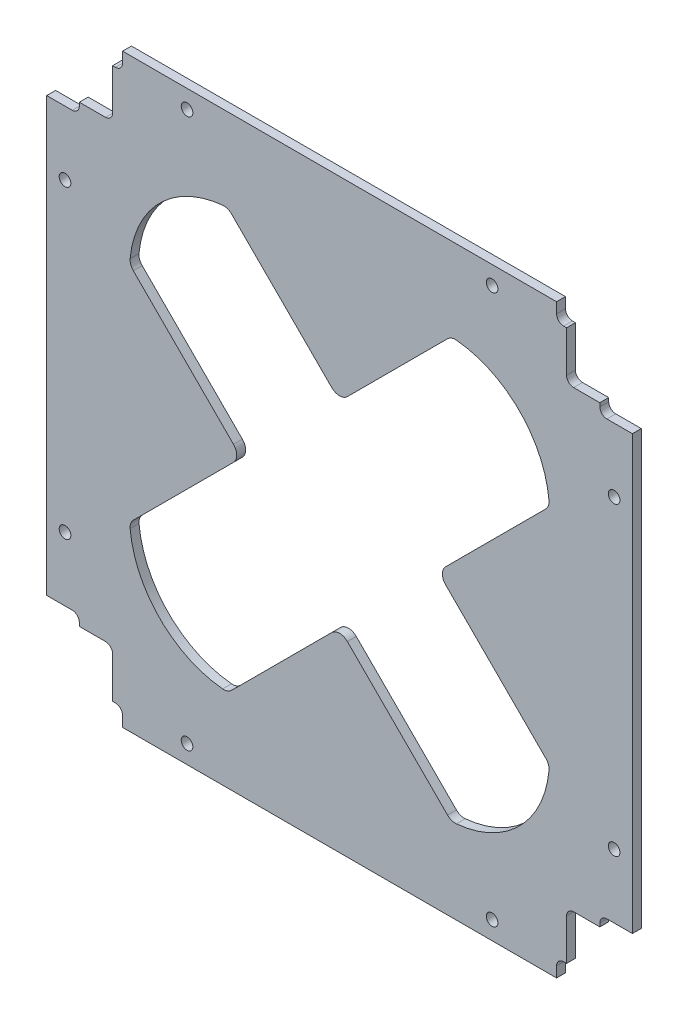
SolidWorks part; units mm, degrees
material "FR4_stuffedProtoboard"
ref_plane "Front Plane" through (0, 0, 0) normal (0, 0, 1) x (1, 0, 0)
ref_plane "Top Plane" through (0, 0, 0) normal (0, 1, 0) x (1, 0, 0)
ref_plane "Right Plane" through (0, 0, 0) normal (1, 0, 0) x (0, 0, -1)
sketch "Sketch1" plane through (0, 0, 0) normal (0, 0, 1) x (1, 0, 0)
  line L0 (53, 53) -> (-53, -53) construction
  line L1 (53, 53) -> (-53, 53)
  line L2 (53, 53) -> (53, -53)
  line L3 (53, -53) -> (-53, -53)
  line L4 (-53, 53) -> (-53, -53)
  point P4 (0, 0)
  dimension "D1" = 106
  dimension "D2" = 106
extrude "mainOutline" add sketch "Sketch1" along normal blind 1.6
sketch "axisLabels" plane through (0, 0, 0) normal (0, 0, -1) x (-1, 0, 0)
  text T0 "+Y"
  text T1 "+X"
sketch "Sketch4" plane through (0, 0, 0) normal (0, 0, -1) x (-1, 0, 0)
  line L10 (-53, 53) -> (53, 53) construction
  line L29 (41.3, 53) -> (41.3, 41.3)
  line L31 (53, 41.3) -> (41.3, 41.3)
  line L46 (53, 53) -> (53, -53) construction
  line L51 (53, 41.3) -> (53, 53)
  line L52 (53, 53) -> (41.3, 53)
  dimension "D11" = 11.7
  dimension "D12" = 11.7
extrude "railCutouts" cut sketch "Sketch4" against normal through all
sketch "Sketch13" plane through (0, 0, 0) normal (0, 0, -1) x (-1, 0, 0)
  line L0 (47.3, 39.4) -> (47.3, 41.3)
  line L2 (53, 41.3) -> (53, 39.4)
  line L5 (41.3, 53) -> (39.5, 53)
  line L6 (41.3, 53) -> (41.3, 50)
  line L7 (41.3, 50) -> (39.5, 50)
  line L8 (39.5, 53) -> (39.5, 50)
  line L9 (53, 41.3) -> (53, -53) construction
  line L10 (53, 41.3) -> (47.3, 41.3)
  line L12 (53, 39.4) -> (47.3, 39.4)
  line L13 (41.3, 41.3) -> (53, 41.3) construction
  point P1 (0, 0)
  point P3 (47.3, 41.3)
  point P17 (47.15, 41.3)
  dimension "D1" = 5.7
  dimension "D3" = 1.9
  dimension "D5" = 1.8
  dimension "D6" = 3
extrude "filletCutouts" cut sketch "Sketch13" against normal through all both and the other way through all
sketch "Sketch5" plane through (0, 0, 0) normal (0, 0, -1) x (-1, 0, 0)
  line L23 (42.198, 42.198) -> (45.4803, 45.4803) construction
  line L24 (41.3, 43.0961) -> (44.5823, 46.3784)
  line L25 (43.0961, 41.3) -> (46.3784, 44.5823)
  line L41 (41.3, 50) -> (41.3, 41.3) construction
  arc A14 (41.3, 43.0961) -> (43.0961, 41.3) centre (42.198, 42.198) ccw
  arc A15 (46.3784, 44.5823) -> (44.5823, 46.3784) centre (45.4803, 45.4803) ccw
  point P0 (41.3, 41.3)
  point P52 (43.8392, 43.8392)
  dimension "D14" = 1.27
  dimension "D7" = 45
extrude "dogbone" [suppressed] cut sketch "Sketch5" against normal through all
sketch "Sketch14" plane through (0, 0, 1.6) normal (0, 0, 1) x (1, 0, 0)
  point P1 (-47.3, 39.4)
sketch "Sketch27" plane through (0, 0, 1.6) normal (0, 0, 1) x (1, 0, 0)
  line L0 (-40.928, 42.198) -> (-40.928, 49.628)
  line L1 (-48.198, 39.028) -> (-53, 39.028)
  line L2 (-53, 39.4) -> (-53, -53) construction
  line L3 (-53, 39.028) -> (-53, 53)
  line L4 (-53, 53) -> (-39.128, 53)
  line L5 (-39.128, 53) -> (-39.128, 50.898)
  line L6 (-40.928, 49.628) -> (-40.398, 49.628)
  line L7 (-42.198, 40.928) -> (-46.928, 40.928)
  line L8 (-46.928, 40.928) -> (-46.928, 40.298)
  line L10 (53, 53) -> (-39.5, 53) construction
  arc A0 (-42.198, 40.928) -> (-40.928, 42.198) centre (-42.198, 42.198) ccw
  arc A1 (-40.398, 49.628) -> (-39.128, 50.898) centre (-40.398, 50.898) ccw
  arc A2 (-48.198, 39.028) -> (-46.928, 40.298) centre (-48.198, 40.298) ccw
  point P7 (0, 0)
  dimension "D1" = 1.27
extrude "smoothCorner" cut sketch "Sketch27" against normal blind 10
pattern_sketch "Sketch-Pattern1" [suppressed] of bodies 103 driven by "Sketch14"
mirror "Mirror1" about plane through (0, 0, 0) normal (1, 0, 0) of "smoothCorner", "filletCutouts", "railCutouts"
mirror "Mirror2" about plane through (0, 0, 0) normal (0, 1, 0) of "Mirror1"
fillet "Fillet1" [suppressed] radius 0.5
sketch "Sketch6" [suppressed] plane through (0, 0, 0) normal (0, 0, -1) x (-1, 0, 0)
  line L0 (-39, 50) -> (-39, 53) construction
  line L1 (-39, 49) -> (-39, 53) construction
  line L2 (-53, 53) -> (41.3, 53) construction
  line L3 (-40, 50) -> (-40, 53)
  line L4 (-38, 50) -> (-38, 53)
  line L5 (-49, 39) -> (-53, 39) construction
  line L6 (-53, 39) -> (-48, 39) construction
  line L7 (-49, 38) -> (-53, 38)
  line L8 (-49, 40) -> (-53, 40)
  line L9 (-49, -39) -> (-55.2142, -39) construction
  line L10 (-48, -39) -> (-53, -39) construction
  line L11 (-49, -40) -> (-55.2142, -40)
  line L12 (-49, -38) -> (-55.2142, -38)
  line L13 (-39, -50) -> (-39, -53.9161) construction
  line L14 (-39, -53) -> (-39, -49) construction
  line L15 (-38, -50) -> (-38, -53.9161)
  line L16 (-40, -50) -> (-40, -53.9161)
  line L17 (39, -50.9) -> (39, -54.538) construction
  line L18 (39, -49.9) -> (39, -53) construction
  line L19 (40, -50.9) -> (40, -54.538)
  line L20 (38, -50.9) -> (38, -54.538)
  line L21 (49, -40.5) -> (54.2026, -40.5) construction
  line L22 (53, -40.5) -> (48, -40.5) construction
  line L23 (49, -39.5) -> (54.2026, -39.5)
  line L24 (49, -41.5) -> (54.2026, -41.5)
  line L25 (49, 40.5) -> (54.5566, 40.5) construction
  line L26 (48, 40.5) -> (53, 40.5) construction
  line L27 (49, 41.5) -> (54.5566, 41.5)
  line L28 (49, 39.5) -> (54.5566, 39.5)
  line L29 (39, 50.9) -> (39, 55.8281) construction
  line L30 (39, 53) -> (39, 49.9) construction
  line L31 (38, 50.9) -> (38, 55.8281)
  line L32 (40, 50.9) -> (40, 55.8281)
  line L33 (-48, -41.4) -> (-48, -39) construction
  line L34 (-39, -49) -> (-41.4, -49) construction
  line L35 (41.4, -49.9) -> (39, -49.9) construction
  line L36 (48, -40.5) -> (48, -41.4) construction
  line L37 (48, 41.4) -> (48, 40.5) construction
  line L38 (39, 49.9) -> (41.4, 49.9) construction
  arc A0 (-40, 50) -> (-38, 50) centre (-39, 50) ccw
  arc A1 (-38, 53) -> (-40, 53) centre (-39, 53) ccw
  arc A2 (-49, 38) -> (-49, 40) centre (-49, 39) ccw
  arc A3 (-53, 40) -> (-53, 38) centre (-53, 39) ccw
  arc A4 (-49, -40) -> (-49, -38) centre (-49, -39) ccw
  arc A5 (-55.2142, -38) -> (-55.2142, -40) centre (-55.2142, -39) ccw
  arc A6 (-38, -50) -> (-40, -50) centre (-39, -50) ccw
  arc A7 (-40, -53.9161) -> (-38, -53.9161) centre (-39, -53.9161) ccw
  arc A8 (40, -50.9) -> (38, -50.9) centre (39, -50.9) ccw
  arc A9 (38, -54.538) -> (40, -54.538) centre (39, -54.538) ccw
  arc A10 (49, -39.5) -> (49, -41.5) centre (49, -40.5) ccw
  arc A11 (54.2026, -41.5) -> (54.2026, -39.5) centre (54.2026, -40.5) ccw
  arc A12 (49, 41.5) -> (49, 39.5) centre (49, 40.5) ccw
  arc A13 (54.5566, 39.5) -> (54.5566, 41.5) centre (54.5566, 40.5) ccw
  arc A14 (38, 50.9) -> (40, 50.9) centre (39, 50.9) ccw
  arc A15 (40, 55.8281) -> (38, 55.8281) centre (39, 55.8281) ccw
  point P6 (-39, 51.5)
  point P11 (-51, 39)
  point P21 (-52.1071, -39)
  point P30 (-39, -51.958)
  point P39 (39, -52.719)
  point P48 (51.6013, -40.5)
  point P57 (51.7783, 40.5)
  point P66 (39, 53.364)
  point P75 (-39, 49)
  dimension "D1" = 1
extrude "solarFillets" [suppressed] cut sketch "Sketch6" against normal through all
fillet "handlingFillets" [suppressed] radius 1
sketch "Sketch7" plane through (0, 0, 1.6) normal (0, 0, 1) x (1, 0, 0)
  line L0 (-39.128, -53) -> (39.128, -53) construction
  line L1 (-53, 39.028) -> (-53, -39.028) construction
  line L2 (39.128, 53) -> (-39.128, 53) construction
  line L3 (-31.37, 28.67) -> (-31.37, 31.21) construction
  line L4 (-31.37, 31.21) -> (-28.83, 31.21) construction
  line L5 (-28.83, 31.21) -> (-28.83, 28.67) construction
  line L6 (-28.83, 28.67) -> (-31.37, 28.67) construction
  line L7 (-31.37, 28.67) -> (-28.83, 31.21) construction
  circle A1 centre (-28.4723, -17.925) radius 0.8
  circle A3 centre (-28.4723, -33.775) radius 0.8
  circle A5 centre (-31.37, 28.67) radius 0.425
  circle A7 centre (-28.83, 28.67) radius 0.425
  circle A9 centre (-30.1, 29.94) radius 0.425
  circle A10 centre (-28.83, 31.21) radius 0.425
  circle A11 centre (-31.37, 31.21) radius 0.425
  circle A12 centre (-31.37, 21.27) radius 0.425
  circle A13 centre (-28.83, 21.27) radius 0.425
  circle A14 centre (-30.1, 22.54) radius 0.425
  circle A15 centre (-28.83, 23.81) radius 0.425
  circle A16 centre (-31.37, 23.81) radius 0.425
  circle A17 centre (-31.37, 13.87) radius 0.425
  circle A18 centre (-28.83, 13.87) radius 0.425
  circle A19 centre (-30.1, 15.14) radius 0.425
  circle A20 centre (-28.83, 16.41) radius 0.425
  circle A21 centre (-31.37, 16.41) radius 0.425
  point P13 (-30.1, 29.94)
  dimension "D8" = 1.6
  dimension "D9" = 3
  dimension "D6" = 0.85
  dimension "D1" = 19.225
  dimension "D2" = 24.5277
  dimension "D3" = 15.85
  dimension "D4" = 23.06
  dimension "D5" = 22.9
  dimension "D7" = 2.54
  dimension "D10" = 7.4
extrude "connectorHoles" [suppressed] cut sketch "Sketch7" against normal through all
hole_wizard "M2 Clearance Hole1" positions "Sketch8" profile "Sketch9" hole size "M2" standard "ANSI Metric" end condition through all
sketch "Sketch8" plane through (0, 0, 0) normal (0, 0, -1) x (-1, 0, 0)
  line L0 (53, 39.028) -> (53, -39.028) construction
  line L1 (39.128, -53) -> (-39.128, -53) construction
  line L2 (-53, -39.028) -> (-53, 39.028) construction
  line L3 (53, 0) -> (-53, 0) construction
  line L5 (0, -53) -> (0, -11.6379) construction
  line L6 (53, 39.028) -> (53, -39.028) construction
  point P0 (49.5, -27.5)
  point P1 (27.5, -49.5)
  point P5 (-49.5, -27.5)
  point P30 (-27.5, -49.5)
  point P31 (-27.5, 49.5)
  point P32 (-49.5, 27.5)
  point P33 (27.5, 49.5)
  point P34 (49.5, 27.5)
  dimension "D1" = 3.5
  dimension "D2" = 3.5
  dimension "D3" = 55
  dimension "D4" = 3.5
  dimension "D5" = 55
  dimension "D6" = 55
sketch "Sketch9" plane through (-49.5, -27.5, 0) normal (1, 0, 0) x (0, 1, 0)
  line L0 (0, 0) -> (0, 1.6)
  line L1 (0, 1.6) -> (1.05, 1.6)
  line L2 (1.05, 1.6) -> (1.05, 0)
  line L5 (1.05, 0) -> (0, 0)
  line L11 (0, -6.35) -> (0, 107.95) construction
  dimension "Thru Hole Dia." = 2.1
  dimension "Thru Hole Depth" = 1.6
sketch "Sketch12" plane through (0, 0, 1.6) normal (0, 0, 1) x (1, 0, 0)
  line L1 (-39.128, -53) -> (39.128, -53) construction
  line L2 (53, -39.028) -> (53, 39.028) construction
  circle A0 centre (27.815, -42.5) radius 0.8
  circle A1 centre (38.585, -42.5) radius 0.8
  dimension "D1" = 1.6
  dimension "D2" = 10.77
  dimension "D3" = 10.5
  dimension "D4" = 25.185
extrude "interboardConnectorHoles" [suppressed] cut sketch "Sketch12" against normal through all both and the other way through all
sketch "Sketch17" [suppressed] plane through (0, 0, 1.6) normal (0, 0, 1) x (1, 0, 0)
  line L1 (-35.8, -40) -> (-21.8, -40)
  line L2 (-35.8, -40) -> (-35.8, -45)
  line L3 (-35.8, -45) -> (-21.8, -45)
  line L4 (-21.8, -40) -> (-21.8, -45)
  line L5 (-41.3, -50) -> (-41.3, -43.2836) construction
  line L6 (-38.9, -53) -> (38.9, -53) construction
  dimension "D1" = 8
  dimension "D2" = 13
  dimension "D3" = 19.5
  dimension "D4" = 14
  dimension "D5" = 5.5
extrude "Cut-Extrude7" [suppressed] cut sketch "Sketch17" against normal through all both and the other way through all
fillet "Fillet2" [suppressed] radius 1.27
sketch "Sketch11" [suppressed] plane through (0, 0, 0) normal (0, 0, -1) x (-1, 0, 0)
  circle A0 centre (0, 0) radius 36
  dimension "D1" = 72
extrude "Cut-Extrude2" [suppressed] cut sketch "Sketch11" against normal through all both and the other way through all
sketch "Sketch15" plane through (0, 0, 0) normal (0, 0, -1) x (-1, 0, 0)
  line L0 (-39.128, 53) -> (39.128, 53) construction
  line L1 (45, 53) -> (-45, 53)
  line L2 (45, 53) -> (45, 46.8)
  line L3 (45, 46.8) -> (-45, 46.8)
  line L4 (-45, 53) -> (-45, 46.8)
  line L5 (45, -53) -> (-45, -53)
  line L6 (45, -53) -> (45, -46.8)
  line L7 (45, -46.8) -> (-45, -46.8)
  line L8 (-45, -53) -> (-45, -46.8)
  line L9 (39.128, -53) -> (-39.128, -53) construction
  line L10 (-53, -39.028) -> (-53, 39.028) construction
  line L11 (-53, 45) -> (-47.8, 45)
  line L12 (-53, 45) -> (-53, -45)
  line L13 (-53, -45) -> (-47.8, -45)
  line L14 (-47.8, 45) -> (-47.8, -45)
  line L15 (53, 45) -> (47.8, 45)
  line L16 (53, 45) -> (53, -45)
  line L17 (53, -45) -> (47.8, -45)
  line L18 (47.8, 45) -> (47.8, -45)
  line L19 (53, 39.028) -> (53, -39.028) construction
  point P8 (0, 53)
  point P11 (0, -53)
  point P22 (-53, 0)
  point P25 (53, 0)
  dimension "D1" = 90
  dimension "D3" = 6.2
  dimension "D5" = 5.2
extrude "Cut-Extrude5" cut sketch "Sketch15" against normal blind 0.001
sketch "Sketch18" [suppressed] plane through (0, 0, 1.6) normal (0, 0, 1) x (1, 0, 0)
  line L0 (-43.2836, -41.3) -> (-46.4, -41.3) construction
  line L1 (-44.8418, -41.3) -> (-41.3, -41.3)
  line L2 (-44.8418, -41.3) -> (-44.8418, -36.3)
  line L3 (-44.8418, -36.3) -> (-41.3, -36.3)
  line L4 (-41.3, -41.3) -> (-41.3, -36.3)
  line L5 (-41.3, -50) -> (-41.3, -43.2836) construction
  dimension "D1" = 5
extrude "Boss-Extrude1" [suppressed] add sketch "Sketch18" against normal up to surface (1.6 mm away) up to face at (0, 0, 0)
sketch "Sketch16" [suppressed] plane through (0, 0, 1.6) normal (0, 0, 1) x (1, 0, 0)
  line L4 (-45, -53) -> (45, -53)
  line L5 (45, -53) -> (45, -46.8)
  line L6 (45, -46.8) -> (-45, -46.8)
  line L7 (-45, -46.8) -> (-45, -53)
  line L8 (-45, -53) -> (45, -53)
  line L9 (45, -53) -> (45, -46.8)
  line L10 (45, -46.8) -> (-45, -46.8)
  line L11 (-45, -46.8) -> (-45, -53)
  line L12 (45, 53) -> (-45, 53)
  line L13 (45, 46.8) -> (45, 53)
  line L14 (-45, 46.8) -> (45, 46.8)
  line L15 (-45, 53) -> (-45, 46.8)
  line L16 (45, 53) -> (-45, 53)
  line L17 (45, 46.8) -> (45, 53)
  line L18 (-45, 46.8) -> (45, 46.8)
  line L19 (-45, 53) -> (-45, 46.8)
  line L20 (-47.8, 45) -> (-53, 45)
  line L21 (-53, 45) -> (-53, -45)
  line L22 (-53, -45) -> (-47.8, -45)
  line L23 (-47.8, -45) -> (-47.8, 45)
  line L24 (-47.8, 45) -> (-53, 45)
  line L25 (-53, 45) -> (-53, -45)
  line L26 (-53, -45) -> (-47.8, -45)
  line L27 (-47.8, -45) -> (-47.8, 45)
  line L28 (53, 45) -> (47.8, 45)
  line L29 (47.8, 45) -> (47.8, -45)
  line L30 (47.8, -45) -> (53, -45)
  line L31 (53, -45) -> (53, 45)
  line L32 (53, 45) -> (47.8, 45)
  line L33 (47.8, 45) -> (47.8, -45)
  line L34 (47.8, -45) -> (53, -45)
  line L35 (53, -45) -> (53, 45)
  dimension "D1" = 0
  dimension "D2" = 0
  dimension "D3" = 0
  dimension "D4" = 0
extrude "Cut-Extrude6" [suppressed] cut sketch "Sketch16" against normal blind 0.001
sketch "Sketch19" plane through (0, 0, 0) normal (0, 0, 1) x (1, 0, 0)
  line L50 (14, -4) -> (6, -4) construction
  line L51 (32, -13.5731) -> (32, -10.1269) construction
  line L54 (0, -16.7) -> (0, -7) construction
  line L55 (6, -19.7) -> (14, -19.7) construction
  line L80 (14, -4) -> (6, -4) construction
  line L81 (32, -13.5731) -> (32, -10.1269) construction
  line L89 (0, -16.7) -> (0, -7) construction
  line L90 (6, -19.7) -> (14, -19.7) construction
  line L91 (0, -4) -> (36, -4)
  line L92 (0, -4) -> (0, -19.7)
  line L93 (0, -19.7) -> (36, -19.7)
  line L106 (-1, -3) -> (-1, -20.7)
  line L107 (-1, -20.7) -> (36.6053, -20.7)
  line L108 (-1, -3) -> (36.6053, -3)
  line L109 (-3, 1) -> (-20.7, 1)
  line L110 (-3, 1) -> (-3, -36.6053)
  line L111 (-20.7, 1) -> (-20.7, -36.6053)
  line L112 (1, 3) -> (1, 20.7)
  line L113 (1, 3) -> (-36.6053, 3)
  line L114 (1, 20.7) -> (-36.6053, 20.7)
  line L115 (3, -1) -> (20.7, -1)
  line L116 (3, -1) -> (3, 36.6053)
  line L117 (20.7, -1) -> (20.7, 36.6053)
  arc A9 (36, -4) -> (36, -19.7) centre (20.3594, -11.85) cw
  arc A13 (36.6053, -3) -> (36.6053, -20.7) centre (20.3594, -11.85) cw
  arc A14 (-3, -36.6053) -> (-20.7, -36.6053) centre (-11.85, -20.3594) cw
  arc A15 (-36.6053, 3) -> (-36.6053, 20.7) centre (-20.3594, 11.85) cw
  arc A16 (3, 36.6053) -> (20.7, 36.6053) centre (11.85, 20.3594) cw
  dimension "D1" = 17.5
  dimension "D2" = 36
  dimension "D3" = 1
  dimension "D4" = 4
sketch "Sketch21" plane through (0, 0, 0) normal (0, 0, 1) x (1, 0, 0)
  circle A0 centre (0, 0) radius 22.5
  dimension "D1" = 45
extrude "Cut-Extrude10" [suppressed] cut sketch "Sketch21" against normal through all and the other way through all
sketch "Sketch22" [suppressed] plane through (0, 0, 1.6) normal (0, 0, 1) x (1, 0, 0)
  line L0 (21.5668, -46.3155) -> (46.3155, -21.5668)
  line L1 (38.5373, -13.7886) -> (46.3155, -21.5668) construction
  line L2 (21.5668, -46.3155) -> (-12.3744, -12.3744)
  line L3 (13.7886, -38.5373) -> (38.5373, -13.7886) construction
  line L4 (13.7886, -38.5373) -> (38.5373, -13.7886) construction
  line L5 (-12.3744, -12.3744) -> (12.3744, 12.3744)
  line L6 (12.3744, 12.3744) -> (46.3155, -21.5668)
  dimension "D1" = 11
extrude "Cut-Extrude11" [suppressed] cut sketch "Sketch22" against normal through all both and the other way through all
fillet "Fillet4" [suppressed] radius 2
extrude "1U pinwheel turnstile cutout" [suppressed] cut sketch "Sketch19" along normal up to next contours L111 A14 L110 L109 | L107 A13 L108 L106 | L116 A16 L117 L115 | L112 L114 A15 L113
sketch "Sketch26" plane through (0, 0, 1.6) normal (0, 0, 1) x (1, 0, 0)
  line L0 (-16.2988, 0) -> (-36.8049, 20.5061) construction
  line L1 (0, 16.2988) -> (-7.7782, 24.077) construction
  line L2 (-24.077, 7.7782) -> (-16.2988, 0) construction
  line L3 (0, 16.2988) -> (-7.7782, 24.077) construction
  line L4 (-24.077, 7.7782) -> (-16.2988, 0) construction
  line L5 (-20.5061, 36.8049) -> (0, 16.2988) construction
  line L6 (36.8049, 20.5061) -> (16.2988, 0) construction
  line L7 (0, 16.2988) -> (20.5061, 36.8049) construction
  line L8 (20.5061, -36.8049) -> (0, -16.2988) construction
  line L9 (16.2988, 0) -> (36.8049, -20.5061) construction
  line L10 (-36.8049, -20.5061) -> (-16.2988, 0) construction
  line L11 (0, -16.2988) -> (-20.5061, -36.8049) construction
  line L12 (-17.713, 0) -> (-37.8275, 20.1145)
  line L13 (-20.1145, 37.8275) -> (0, 17.713)
  line L14 (0, 17.713) -> (20.1145, 37.8275)
  line L15 (37.8275, 20.1145) -> (17.713, 0)
  line L16 (17.713, 0) -> (37.8275, -20.1145)
  line L17 (20.1145, -37.8275) -> (0, -17.713)
  line L18 (0, -17.713) -> (-20.1145, -37.8275)
  line L19 (-37.8275, -20.1145) -> (-17.713, 0)
  arc A0 (-17.1196, 32.4741) -> (-32.4741, 17.1196) centre (-16.2012, 16.2012) ccw construction
  arc A1 (-17.1196, 32.4741) -> (-32.4741, 17.1196) centre (-16.2012, 16.2012) ccw construction
  arc A2 (-36.8049, 20.5061) -> (-20.5061, 36.8049) centre (-19.3436, 19.3436) cw construction
  arc A3 (20.5061, 36.8049) -> (36.8049, 20.5061) centre (19.3436, 19.3436) cw construction
  arc A4 (36.8049, -20.5061) -> (20.5061, -36.8049) centre (19.3436, -19.3436) cw construction
  arc A5 (-20.5061, -36.8049) -> (-36.8049, -20.5061) centre (-19.3436, -19.3436) cw construction
  arc A6 (-37.8275, 20.1145) -> (-20.1145, 37.8275) centre (-19.3436, 19.3436) cw
  arc A7 (20.1145, 37.8275) -> (37.8275, 20.1145) centre (19.3436, 19.3436) cw
  arc A8 (37.8275, -20.1145) -> (20.1145, -37.8275) centre (19.3436, -19.3436) cw
  arc A9 (-20.1145, -37.8275) -> (-37.8275, -20.1145) centre (-19.3436, -19.3436) cw
  dimension "D1" = 17.5
  dimension "D3" = 4
  dimension "D2" = 29
  dimension "D4" = 1
extrude "1I circular turnstile cutout" cut sketch "Sketch26" against normal blind 10
sketch "Sketch25" [suppressed] plane through (0, 0, 0) normal (0, 0, -1) x (-1, 0, 0)
  line L0 (36.332, -29.0597) -> (36.332, -25.6135) construction
  line L1 (10.332, -35.1866) -> (18.332, -35.1866) construction
  line L2 (18.332, -19.4866) -> (10.332, -19.4866) construction
  line L3 (4.332, -32.1866) -> (4.332, -22.4866) construction
  line L4 (36.332, -29.0597) -> (36.332, -25.6135) construction
  line L5 (10.332, -35.1866) -> (18.332, -35.1866) construction
  line L6 (18.332, -19.4866) -> (10.332, -19.4866) construction
  line L7 (4.332, -32.1866) -> (4.332, -22.4866) construction
  line L8 (40.332, -35.1866) -> (4.332, -35.1866) construction
  line L9 (4.332, -35.1866) -> (4.332, -19.4866) construction
  line L10 (4.332, -19.4866) -> (40.332, -19.4866) construction
  line L11 (40.9373, -36.1866) -> (3.332, -36.1866)
  line L12 (3.332, -36.1866) -> (3.332, -18.4866)
  line L13 (3.332, -18.4866) -> (40.9373, -18.4866)
  line L14 (-18.4866, -3.332) -> (-18.4866, -40.9373)
  line L15 (-36.1866, -3.332) -> (-18.4866, -3.332)
  line L16 (-36.1866, -40.9373) -> (-36.1866, -3.332)
  line L17 (-3.332, 18.4866) -> (-40.9373, 18.4866)
  line L18 (-3.332, 36.1866) -> (-3.332, 18.4866)
  line L19 (-40.9373, 36.1866) -> (-3.332, 36.1866)
  line L20 (18.4866, 3.332) -> (18.4866, 40.9373)
  line L21 (36.1866, 3.332) -> (18.4866, 3.332)
  line L22 (36.1866, 40.9373) -> (36.1866, 3.332)
  arc A0 (40.332, -19.4866) -> (40.332, -35.1866) centre (24.6914, -27.3366) cw construction
  arc A1 (40.9373, -18.4866) -> (40.9373, -36.1866) centre (24.6914, -27.3366) cw
  arc A2 (-18.4866, -40.9373) -> (-36.1866, -40.9373) centre (-27.3366, -24.6914) cw
  arc A3 (-40.9373, 18.4866) -> (-40.9373, 36.1866) centre (-24.6914, 27.3366) cw
  arc A4 (18.4866, 40.9373) -> (36.1866, 40.9373) centre (27.3366, 24.6914) cw
  dimension "D1" = 17.5
  dimension "D2" = 36
  dimension "D3" = 1
  dimension "D4" = 4
extrude "2U turnstile cutout" [suppressed] cut sketch "Sketch25" against normal up to next
sketch "Sketch23" [suppressed] plane through (0, 0, 1.6) normal (0, 0, 1) x (1, 0, 0)
  line L0 (-20.7, -36.6053) -> (-20.7, 1) construction
  line L1 (-20.7, -20.7) -> (20.7, -20.7)
  line L2 (-20.7, -20.7) -> (-20.7, 20.7)
  line L3 (-20.7, 20.7) -> (20.7, 20.7)
  line L4 (20.7, -20.7) -> (20.7, 20.7)
  line L5 (-36.6053, 20.7) -> (1, 20.7) construction
  line L6 (36.6053, -20.7) -> (-1, -20.7) construction
  line L7 (20.7, 36.6053) -> (20.7, -1) construction
extrude "Cut-Extrude16" [suppressed] cut sketch "Sketch23" against normal blind 10
fillet "Fillet5" [suppressed] radius 1
sketch "Sketch24" plane through (0, 0, 1.6) normal (0, 0, 1) x (1, 0, 0)
  line L0 (-53, -39.028) -> (-53, 39.028) construction
  line L1 (52.8, 52.8) -> (-52.8, 52.8)
  line L2 (52.8, 52.8) -> (52.8, -52.8)
  line L3 (52.8, -52.8) -> (-52.8, -52.8)
  line L4 (-52.8, 52.8) -> (-52.8, -52.8)
  line L5 (-39.128, 53) -> (39.128, 53) construction
  line L6 (53, 39.028) -> (53, -39.028) construction
  line L7 (39.128, -53) -> (-39.128, -53) construction
  dimension "D1" = 0.2
  dimension "D2" = 0.2
  dimension "D3" = 0.2
  dimension "D4" = 0.2
extrude "Cut-Extrude19" cut sketch "Sketch24" against normal through all flip side to cut
fillet "Fillet7" [suppressed] radius 0.5
fillet "Fillet8" [suppressed] radius 1
fillet "Fillet9" radius 2 12 edges at (0, -17.713, 0.8) (17.713, 0, 0.8) (-17.713, 0, 0.8) (0, 17.713, 0.8) (-37.8275, -20.1145, 0.8) (-20.1145, -37.8275, 0.8) (20.1145, -37.8275, 0.8) (37.8275, -20.1145, 0.8) (37.8275, 20.1145, 0.8) (20.1145, 37.8275, 0.8) (-37.8275, 20.1145, 0.8) (-20.1145, 37.8275, 0.8)
